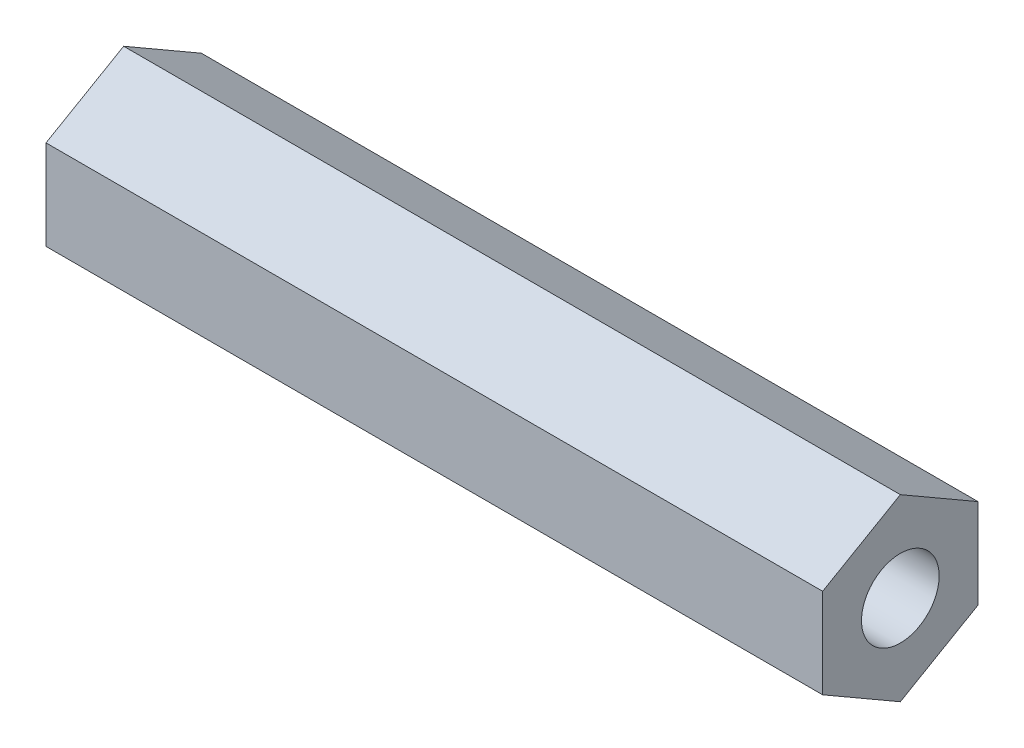
SolidWorks part; units mm, degrees
ref_plane "Front Plane" through (0, 0, 0) normal (0, 0, 1) x (1, 0, 0)
ref_plane "Top Plane" through (0, 0, 0) normal (0, 1, 0) x (1, 0, 0)
ref_plane "Right Plane" through (0, 0, 0) normal (1, 0, 0) x (0, 0, -1)
sketch "Sketch1" plane through (0, 0, 0) normal (1, 0, 0) x (0, 0, -1)
  line L7 (-42.7283, 8.2771) -> (-45.7283, 6.5451)
  line L8 (-45.7283, 6.5451) -> (-45.7283, 3.081)
  line L9 (-45.7283, 3.081) -> (-42.7283, 1.3489)
  line L10 (-42.7283, 1.3489) -> (-39.7283, 3.081)
  line L11 (-39.7283, 3.081) -> (-39.7283, 6.5451)
  line L12 (-39.7283, 6.5451) -> (-42.7283, 8.2771)
  circle A0 centre (-42.7283, 4.813) radius 1.5
  circle A2 centre (-42.7283, 4.813) radius 3 construction
  point P2 (0, 0)
  dimension "D1" = 3
extrude "Boss-Extrude1" add sketch "Sketch1" along normal blind 30
